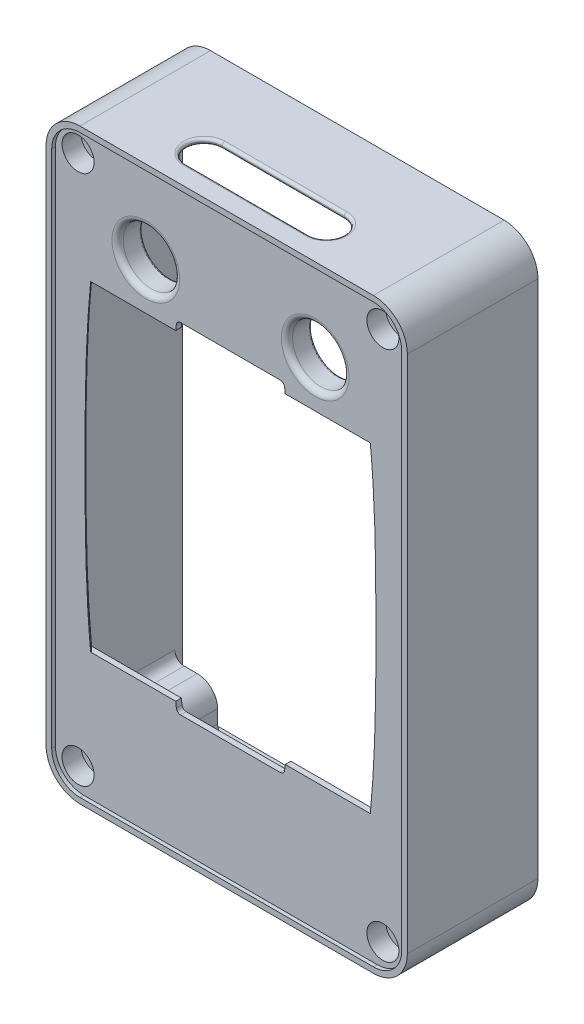
SolidWorks part; units mm, degrees
ref_plane "Front" through (0, 0, 0) normal (0, 0, 1) x (1, 0, 0)
ref_plane "Top" through (0, 0, 0) normal (0, 1, 0) x (1, 0, 0)
ref_plane "Right" through (0, 0, 0) normal (1, 0, 0) x (0, 0, -1)
sketch "Sketch1" plane through (0, 0, 0) normal (0, 0, 1) x (1, 0, 0)
  line L0 (74.8, -156) -> (-74.8, -156) construction
  line L1 (78, 156) -> (-78, 156)
  line L2 (96, 138) -> (96, -138)
  line L3 (78, -156) -> (-78, -156)
  line L4 (-96, 138) -> (-96, -138)
  line L5 (96, 156) -> (-96, -156) construction
  line L6 (96, -156) -> (-96, 156) construction
  line L7 (-96, -134.8) -> (-96, 134.8) construction
  arc A0 (-78, -156) -> (-96, -138) centre (-78, -138) cw
  arc A1 (-78, 156) -> (-96, 138) centre (-78, 138) ccw
  arc A2 (78, 156) -> (96, 138) centre (78, 138) cw
  arc A3 (96, -138) -> (78, -156) centre (78, -138) cw
  point P0 (0, 0)
  dimension "D1" = 18
  dimension "D2" = 18
extrude "Extrude-Thin1" add sketch "Sketch1" along normal blind 2 and the other way up to surface (67.4 mm away) thin thin type one direction reverse wall 3
sketch "Sketch2" plane through (0, 0, 0) normal (0, 0, 1) x (1, 0, 0)
  line L0 (-78, -153) -> (78, -153) construction
  line L1 (93, -138) -> (93, 138) construction
  line L2 (78, 153) -> (-78, 153) construction
  line L3 (-93, 138) -> (-93, -138) construction
  line L4 (-78, -153) -> (78, -153)
  line L5 (93, -138) -> (93, 138)
  line L6 (78, 153) -> (-78, 153)
  line L7 (-93, 138) -> (-93, -138)
  arc A0 (-93, -138) -> (-78, -153) centre (-78, -138) ccw construction
  arc A1 (78, -153) -> (93, -138) centre (78, -138) ccw construction
  arc A2 (93, 138) -> (78, 153) centre (78, 138) ccw construction
  arc A3 (-78, 153) -> (-93, 138) centre (-78, 138) ccw construction
  arc A4 (-93, -138) -> (-78, -153) centre (-78, -138) ccw
  arc A5 (78, -153) -> (93, -138) centre (78, -138) ccw
  arc A6 (93, 138) -> (78, 153) centre (78, 138) ccw
  arc A7 (-78, 153) -> (-93, 138) centre (-78, 138) ccw
extrude "Boss-Extrude1" add sketch "Sketch2" against normal blind 3
sketch "Sketch3" plane through (0, 0, 0) normal (0, 0, 1) x (1, 0, 0)
  line L20 (-26.4864, -90.3) -> (26.4867, -90.3)
  line L21 (28.7694, -88.2548) -> (29.0928, -85.3)
  line L22 (29.0928, -85.3) -> (74.3238, -85.3)
  line L23 (74.3238, 85.3) -> (29.0928, 85.3)
  line L24 (29.0928, 85.3) -> (28.7693, 88.2552)
  line L25 (26.4865, 90.3) -> (-26.4867, 90.3)
  line L26 (-28.7693, 88.2548) -> (-29.0928, 85.3)
  line L27 (-29.0928, 85.3) -> (-74.3238, 85.3)
  line L28 (-74.3238, -85.3) -> (-29.0928, -85.3)
  line L29 (-29.0928, -85.3) -> (-28.7692, -88.2552)
  line L30 (-26.4864, -90.3) -> (26.4867, -90.3)
  line L31 (28.7694, -88.2548) -> (29.0928, -85.3)
  line L32 (29.0928, -85.3) -> (74.3238, -85.3)
  line L33 (74.3238, 85.3) -> (29.0928, 85.3)
  line L34 (29.0928, 85.3) -> (28.7693, 88.2552)
  line L35 (26.4865, 90.3) -> (-26.4867, 90.3)
  line L36 (-28.7693, 88.2548) -> (-29.0928, 85.3)
  line L37 (-29.0928, 85.3) -> (-74.3238, 85.3)
  line L38 (-74.3238, -85.3) -> (-29.0928, -85.3)
  line L39 (-29.0928, -85.3) -> (-28.7692, -88.2552)
  arc A4 (26.4867, -90.3) -> (28.7694, -88.2548) centre (26.4848, -88.0015) ccw
  arc A5 (28.7693, 88.2552) -> (26.4865, 90.3) centre (26.4848, 88.0015) ccw
  arc A6 (-26.4867, 90.3) -> (-28.7693, 88.2548) centre (-26.4848, 88.0015) ccw
  arc A7 (-28.7692, -88.2552) -> (-26.4864, -90.3) centre (-26.4848, -88.0015) ccw
  arc A8 (26.4867, -90.3) -> (28.7694, -88.2548) centre (26.4848, -88.0015) ccw
  arc A9 (28.7693, 88.2552) -> (26.4865, 90.3) centre (26.4848, 88.0015) ccw
  arc A10 (-26.4867, 90.3) -> (-28.7693, 88.2548) centre (-26.4848, 88.0015) ccw
  arc A11 (-28.7692, -88.2552) -> (-26.4864, -90.3) centre (-26.4848, -88.0015) ccw
  spline S12 degree 3 poles (1671.0741, -1133.0264) (-248.8202, -676.1777) (51.3567, -385.7796) (75.5172, -71.1196) (75.7555, -67.57) (76.3756, -56.9141) (76.6633, -49.8036) (77.058, -35.5775) (77.1662, -28.4619) (79.5582, 253.7203) (11.264, 529.388) (1853.8429, 788.8035) knots -10.838785 -10.838785 -10.838785 -10.838785 0.125 0.125 0.25 0.25 0.5 0.5 0.75 0.75 10.414692 10.414692 10.414692 10.414692 only from (74.3238, -85.3) to (77.3, 0)
  spline S13 degree 3 poles (1850.7327, -796.2534) (11.3398, -528.7126) (79.5572, -253.5407) (77.1662, 28.4652) (77.0579, 35.5807) (76.6632, 49.8078) (76.3754, 56.9185) (75.7554, 67.571) (75.5171, 71.1198) (50.3351, 399.055) (-273.6004, 704.5976) (1645.9373, 1151.5329) knots -9.407198 -9.407198 -9.407198 -9.407198 0.25 0.25 0.5 0.5 0.75 0.75 0.875 0.875 12.30781 12.30781 12.30781 12.30781 only from (77.3, 0) to (74.3238, 85.3)
  spline S14 degree 3 poles (-1671.0704, 1133.0255) (248.8198, 676.1774) (-51.3568, 385.7794) (-75.5172, 71.1196) (-75.7555, 67.57) (-76.3756, 56.9141) (-76.6633, 49.8036) (-77.058, 35.5775) (-77.1662, 28.4619) (-79.5582, -253.7201) (-11.2641, -529.3877) (-1853.8396, -788.8031) knots -10.838777 -10.838777 -10.838777 -10.838777 0.125 0.125 0.25 0.25 0.5 0.5 0.75 0.75 10.414687 10.414687 10.414687 10.414687 only from (-74.3238, 85.3) to (-77.3, 0)
  spline S15 degree 3 poles (-1850.7327, 796.2534) (-11.3398, 528.7126) (-79.5572, 253.5407) (-77.1662, -28.4652) (-77.0579, -35.5807) (-76.6632, -49.8078) (-76.3754, -56.9185) (-75.7554, -67.571) (-75.5171, -71.1198) (-50.3351, -399.055) (273.6004, -704.5976) (-1645.9373, -1151.5329) knots -9.407198 -9.407198 -9.407198 -9.407198 0.25 0.25 0.5 0.5 0.75 0.75 0.875 0.875 12.30781 12.30781 12.30781 12.30781 only from (-77.3, 0) to (-74.3238, -85.3)
  spline S16 degree 3 poles (74.3238, -85.3) (74.6643, -81.7581) (74.9725, -78.2137) (75.5172, -71.1196) (75.7555, -67.57) (76.3756, -56.9141) (76.6633, -49.8036) (77.058, -35.5775) (77.1662, -28.4619) (77.2868, -14.2314) (77.2999, -7.1158) (77.3, 0) knots 0 0 0 0 0.125 0.125 0.25 0.25 0.5 0.5 0.75 0.75 1 1 1 1
  spline S17 degree 3 poles (77.3, 0) (77.2999, 7.1164) (77.2868, 14.2328) (77.1662, 28.4652) (77.0579, 35.5807) (76.6632, 49.8078) (76.3754, 56.9185) (75.7554, 67.571) (75.5171, 71.1198) (74.9724, 78.2132) (74.6643, 81.7576) (74.3238, 85.3) knots 0 0 0 0 0.25 0.25 0.5 0.5 0.75 0.75 0.875 0.875 1 1 1 1
  spline S18 degree 3 poles (-74.3238, 85.3) (-74.6643, 81.7581) (-74.9725, 78.2137) (-75.5172, 71.1196) (-75.7555, 67.57) (-76.3756, 56.9141) (-76.6633, 49.8036) (-77.058, 35.5775) (-77.1662, 28.4619) (-77.2868, 14.2314) (-77.2999, 7.1158) (-77.3, 0) knots 0 0 0 0 0.125 0.125 0.25 0.25 0.5 0.5 0.75 0.75 1 1 1 1
  spline S19 degree 3 poles (-77.3, 0) (-77.2999, -7.1164) (-77.2868, -14.2328) (-77.1662, -28.4652) (-77.0579, -35.5807) (-76.6632, -49.8078) (-76.3754, -56.9185) (-75.7554, -67.571) (-75.5171, -71.1198) (-74.9724, -78.2132) (-74.6643, -81.7576) (-74.3238, -85.3) knots 0 0 0 0 0.25 0.25 0.5 0.5 0.75 0.75 0.875 0.875 1 1 1 1
  dimension "D1" = 0.3
extrude "Cut-Extrude1" cut sketch "Sketch3" against normal through all
sketch "Sketch5" plane through (0, 0, 0) normal (0, 0, 1) x (1, 0, 0)
  line L0 (70.2426, -141) -> (70.2426, -153)
  line L1 (-78, -153) -> (78, -153) construction
  line L2 (81, -130.2426) -> (93, -130.2426)
  line L3 (93, -138) -> (93, 138) construction
  line L4 (93, -138) -> (93, 138) construction
  line L5 (-78, -153) -> (78, -153) construction
  line L6 (93, -138) -> (93, -130.2426)
  line L7 (70.2426, -153) -> (78, -153)
  arc A0 (81, -130.2426) -> (70.2426, -141) centre (81, -141) ccw
  arc A1 (78, -153) -> (93, -138) centre (78, -138) ccw construction
  arc A2 (78, -153) -> (93, -138) centre (78, -138) ccw
extrude "Boss-Extrude2" add sketch "Sketch5" against normal up to surface (63.4 mm away)
sketch "Sketch7" plane through (0, 0, 0) normal (0, 0, 1) x (1, 0, 0)
  circle A0 centre (81, -141) radius 8.5
  dimension "D1" = 17
extrude "Cut-Extrude2" cut sketch "Sketch7" against normal blind 10
sketch "Sketch8" plane through (0, 0, -10) normal (0, 0, 1) x (1, 0, 0)
  circle A0 centre (81, -141) radius 4.5
  dimension "D1" = 9
extrude "Cut-Extrude3" cut sketch "Sketch8" against normal through all
mirror "Mirror1" about plane through (0, 0, 0) normal (1, 0, 0) of "Boss-Extrude2", "Cut-Extrude2", "Cut-Extrude3"
mirror "Mirror2" about plane through (0, 0, 0) normal (0, 1, 0) of "Mirror1", "Boss-Extrude2", "Cut-Extrude2", "Cut-Extrude3"
fillet "Fillet1" radius 5 8 edges at (70.2426, -153, -33.2) (93, -130.2426, -33.2) (-93, -130.2426, -33.2) (-70.2426, -153, -33.2) (-93, 130.2426, -33.2) (-70.2426, 153, -33.2) (70.2426, 153, -33.2) (93, 130.2426, -33.2)
sketch "Sketch9" plane through (0, 0, 0) normal (0, 0, 1) x (1, 0, 0)
  circle A0 centre (-45, 110) radius 15
  dimension "D1" = 30
extrude "Cut-Extrude4" cut sketch "Sketch9" against normal blind 30
mirror "Mirror3" about plane through (0, 0, 0) normal (1, 0, 0) of "Cut-Extrude4"
sketch "Sketch10" plane through (0, 0, -3) normal (0, 0, -1) x (-1, 0, 0)
  circle A0 centre (45, 110) radius 15
  circle A1 centre (45, 110) radius 18
  dimension "D1" = 3
extrude "Boss-Extrude3" add sketch "Sketch10" along normal blind 10
mirror "Mirror4" about plane through (0, 0, 0) normal (1, 0, 0) of "Boss-Extrude3"
fillet "Fillet2" radius 3 2 edges at (30, 110, 0) (-30, 110, 0)
chamfer "Chamfer1" distance 2.5 angle 45 4 edges
fillet "Fillet3" radius 1 4 edges at (60, 110, -13) (-63, 110, -13) (63, 110, -13) (-60, 110, -13)
sketch "Sketch11" plane through (0, 156, 0) normal (0, 1, 0) x (1, 0, 0)
  line L0 (32.5, 28) -> (-32.5, 28) construction
  line L1 (-32.5, 9) -> (32.5, 9) construction
  line L2 (32.5, 28) -> (-32.5, 28)
  line L3 (-32.5, 9) -> (32.5, 9)
  arc A0 (32.5, 9) -> (32.5, 28) centre (32.5, 18.5) ccw construction
  arc A1 (-32.5, 28) -> (-32.5, 9) centre (-32.5, 18.5) ccw construction
  arc A2 (32.5, 9) -> (32.5, 28) centre (32.5, 18.5) ccw
  arc A3 (-32.5, 28) -> (-32.5, 9) centre (-32.5, 18.5) ccw
extrude "Cut-Extrude5" cut sketch "Sketch11" against normal blind 10
fillet "Fillet4" radius 1.5 8 edges at (42, 153, -18.5) (0, 153, -9) (-42, 153, -18.5) (42, 156, -18.5) (0, 156, -9) (-42, 156, -18.5) (0, 153, -28) (0, 156, -28)
